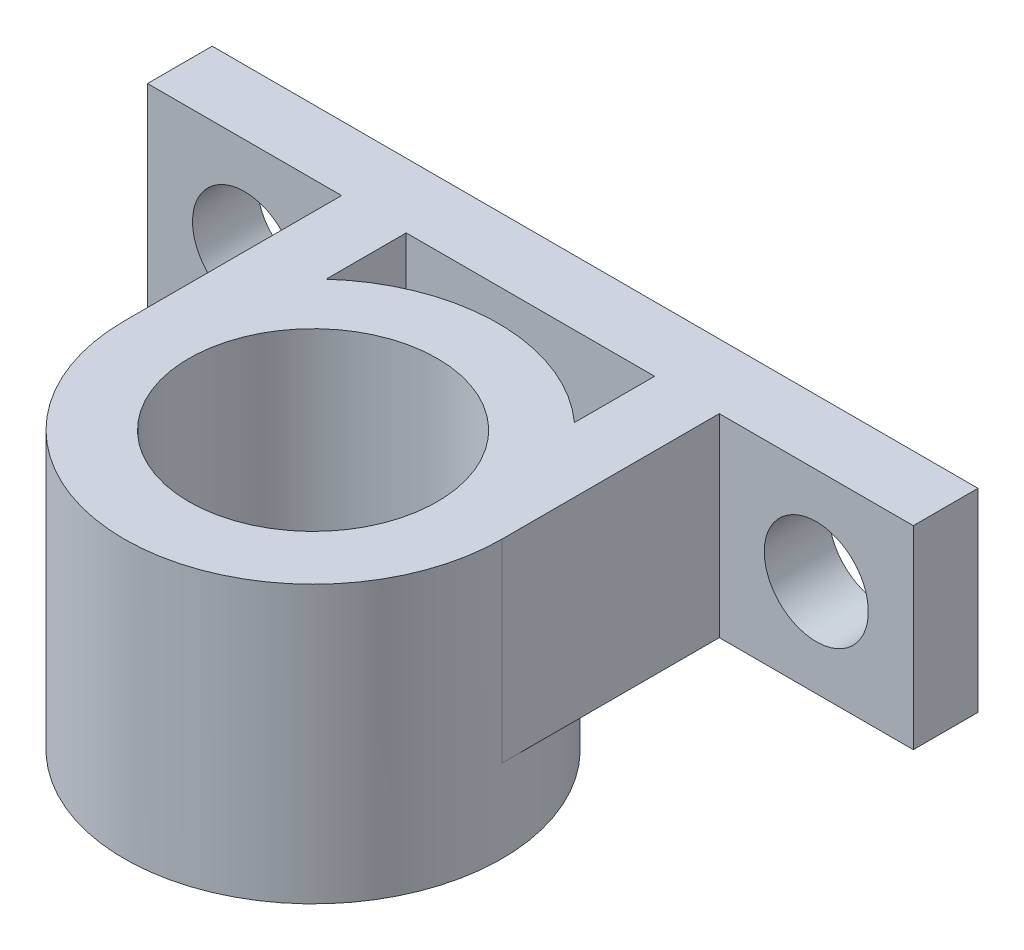
SolidWorks part; units mm, degrees
ref_plane "Front Plane" through (0, 0, 0) normal (0, 0, 1) x (1, 0, 0)
ref_plane "Top Plane" through (0, 0, 0) normal (0, 1, 0) x (1, 0, 0)
ref_plane "Right Plane" through (0, 0, 0) normal (1, 0, 0) x (0, 0, -1)
sketch "Sketch1" plane through (0, 0, 0) normal (0, 1, 0) x (1, 0, 0)
  line L0 (0, 0) -> (14.2506, 0) construction
  line L1 (0, 0) -> (0, 17.6258) construction
  line L3 (-6.096, -0.381) -> (-6.096, 13.843) construction
  line L4 (-9.271, 0) -> (-9.271, 10.668)
  line L5 (-9.271, 10.668) -> (-18.796, 10.668)
  line L6 (-6.096, 13.843) -> (-18.796, 13.843)
  line L7 (-18.796, 10.668) -> (-18.796, 13.843)
  line L9 (-6.096, 13.843) -> (6.096, 13.843)
  line L11 (9.271, 0) -> (9.271, 10.668)
  line L12 (18.796, 10.668) -> (18.796, 13.843)
  line L13 (6.096, 13.843) -> (18.796, 13.843)
  line L14 (9.271, 10.668) -> (18.796, 10.668)
  line L17 (-6.096, 6.731) -> (-6.096, 10.668)
  line L18 (6.096, 6.731) -> (6.096, 10.668)
  line L19 (-6.096, 10.668) -> (6.096, 10.668)
  circle A0 centre (0, 0) radius 6.096
  circle A1 centre (0, 0) radius 9.271 construction
  arc A3 (9.271, 0) -> (-9.271, 0) centre (0, 0) cw
  arc A5 (-6.096, 6.731) -> (6.096, 6.731) centre (0, 0) cw
  point P18 (0, 13.843)
  point P19 (0, 10.668)
  dimension "D1" = 12.192
  dimension "D2" = 3.175
  dimension "D3" = 14.224
  dimension "D4" = 3.175
  dimension "D5" = 12.7
extrude "Boss-Extrude1" add sketch "Sketch1" along normal blind 9.525
sketch "Sketch2" plane through (0, 0, -10.668) normal (0, 0, 1) x (1, 0, 0)
  line L0 (-18.796, 4.7625) -> (-9.271, 4.7625) construction
  line L1 (-18.796, 9.525) -> (-18.796, 0) construction
  line L2 (-9.271, 9.525) -> (-9.271, 0) construction
  line L3 (-14.0335, 9.525) -> (-14.0335, 0) construction
  line L4 (-18.796, 9.525) -> (-9.271, 9.525) construction
  line L5 (-18.796, 0) -> (-9.271, 0) construction
  line L6 (0, 0) -> (0, 9.525) construction
  line L7 (9.271, 9.525) -> (-9.271, 9.525) construction
  circle A0 centre (-14.0335, 4.7625) radius 2.5527
  circle A1 centre (14.0335, 4.7625) radius 2.5527
  dimension "D1" = 5.1054
extrude "Cut-Extrude1" cut sketch "Sketch2" against normal through all
sketch "Sketch3" plane through (0, 0, 0) normal (0, -1, 0) x (-1, 0, 0)
  circle A0 centre (0, 0) radius 6.096
  circle A3 centre (0, 0) radius 9.271
  dimension "D1" = 12.192
  dimension "D2" = 3.175
extrude "Boss-Extrude2" add sketch "Sketch3" along normal blind 2.794
sketch "Sketch4" plane through (0, -2.794, 0) normal (0, -1, 0) x (-1, 0, 0)
  circle A1 centre (0, 0) radius 6.096 construction
  circle A2 centre (0, 0) radius 9.271
  circle A3 centre (0, 0) radius 4.826
  dimension "D1" = 12.192
  dimension "D2" = 3.175
  dimension "D3" = 1.27
extrude "Boss-Extrude3" add sketch "Sketch4" along normal blind 1.27 contours A2 | A3
